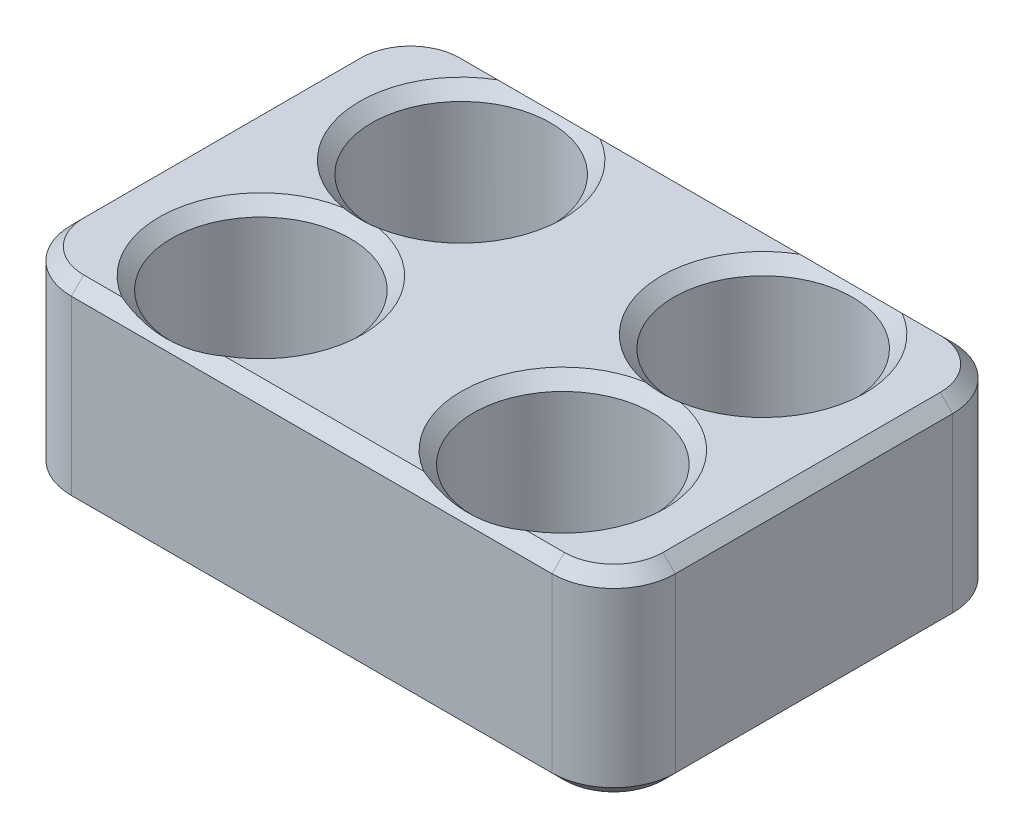
SolidWorks part; units mm, degrees
ref_plane "Front Plane" through (0, 0, 0) normal (0, 0, 1) x (1, 0, 0)
ref_plane "Top Plane" through (0, 0, 0) normal (0, 1, 0) x (1, 0, 0)
ref_plane "Right Plane" through (0, 0, 0) normal (1, 0, 0) x (0, 0, -1)
sketch "Sketch1" plane through (0, 0, 0) normal (0, 1, 0) x (1, 0, 0)
  line L1 (-90, 27.5806) -> (8, 27.5806)
  line L2 (-90, 27.5806) -> (-90, -37.4194)
  line L3 (-90, -37.4194) -> (8, -37.4194)
  line L4 (8, 27.5806) -> (8, -37.4194)
  dimension "D1" = 65
  dimension "D2" = 98
extrude "Boss-Extrude1" add sketch "Sketch1" along normal blind 32
sketch "Sketch2" plane through (0, 32, 0) normal (0, 1, 0) x (1, 0, 0)
  line L0 (-90, -4.9194) -> (8, -4.9194) construction
  line L1 (-90, 27.5806) -> (-90, -37.4194) construction
  line L2 (8, -37.4194) -> (8, 27.5806) construction
  line L3 (8, -4.9194) -> (-41, 27.5806) construction
  line L4 (8, 27.5806) -> (-90, 27.5806) construction
  line L5 (-41, 27.5806) -> (-41, -37.4194) construction
  line L6 (-90, -37.4194) -> (8, -37.4194) construction
  line L7 (-41, -37.4194) -> (-90, -4.9194) construction
  line L8 (-90, -4.9194) -> (-41, 27.5806) construction
  line L9 (-90, 27.5806) -> (-90, -4.9194) construction
  line L10 (-90, -4.9194) -> (-90, 11.3306) construction
  line L11 (-90, 11.3306) -> (-41, 11.3306) construction
  line L12 (-41, 11.3306) -> (8, 11.3306) construction
  circle A0 centre (-16.5, 11.3306) radius 14.5
  circle A1 centre (-16.5, -21.1694) radius 14.5
  circle A2 centre (-65.5, 11.3306) radius 14.5
  circle A3 centre (-65.5, -21.1694) radius 14.5
  dimension "D1" = 29
extrude "Cut-Extrude1" cut sketch "Sketch2" against normal blind 27
fillet "Fillet1" radius 10 1 edges at (8, 16, -27.5806)
fillet "Fillet2" radius 10 1 edges at (-90, 16, 37.4194)
fillet "Fillet3" radius 10 1 edges at (-90, 16, -27.5806)
fillet "Fillet4" radius 10 1 edges at (8, 16, 37.4194)
chamfer "Chamfer1" distance 2 angle 45 24 edges at (-16.5, 5, 6.6694) (-16.5, 5, 3.1694) (-65.5, 5, -25.8306) (-65.5, 5, 35.6694) (-87.0711, 32, 34.4904) (-90, 32, 4.9194) (-87.0711, 32, -24.6517) (-41, 32, -27.5806) (5.0711, 32, -24.6517) (8, 32, 4.9194) (5.0711, 32, 34.4904) (-41, 32, 37.4194) (-16.5, 32, 3.1694) (-65.5, 32, 35.6694) (-65.5, 32, -25.8306) (-16.5, 32, 6.6694) (-90, 0, 4.9194) (-87.0711, 0, 34.4904) (-87.0711, 0, -24.6517) (-41, 0, 37.4194) (-41, 0, -27.5806) (5.0711, 0, 34.4904) (5.0711, 0, -24.6517) (8, 0, 4.9194)
sketch "Sketch3" plane through (0, 0, 0) normal (0, -1, 0) x (1, 0, 0)
  line L0 (-88, 4.9194) -> (6, 4.9194) construction
  line L1 (-88, 27.4194) -> (-88, -17.5806) construction
  line L2 (6, -17.5806) -> (6, 27.4194) construction
  line L15 (-71, -0.0806) -> (-11, -0.0806)
  line L16 (-71, -0.0806) -> (-71, 9.9194)
  line L17 (-71, 9.9194) -> (-11, 9.9194)
  line L18 (-11, -0.0806) -> (-11, 9.9194)
  line L19 (-71, -0.0806) -> (-11, 9.9194) construction
  line L20 (-71, 9.9194) -> (-11, -0.0806) construction
  point P12 (-41, 4.9194)
  dimension "D1" = 10
  dimension "D2" = 60
extrude "Cut-Extrude2" cut sketch "Sketch3" against normal blind 3 from offset 0.5
